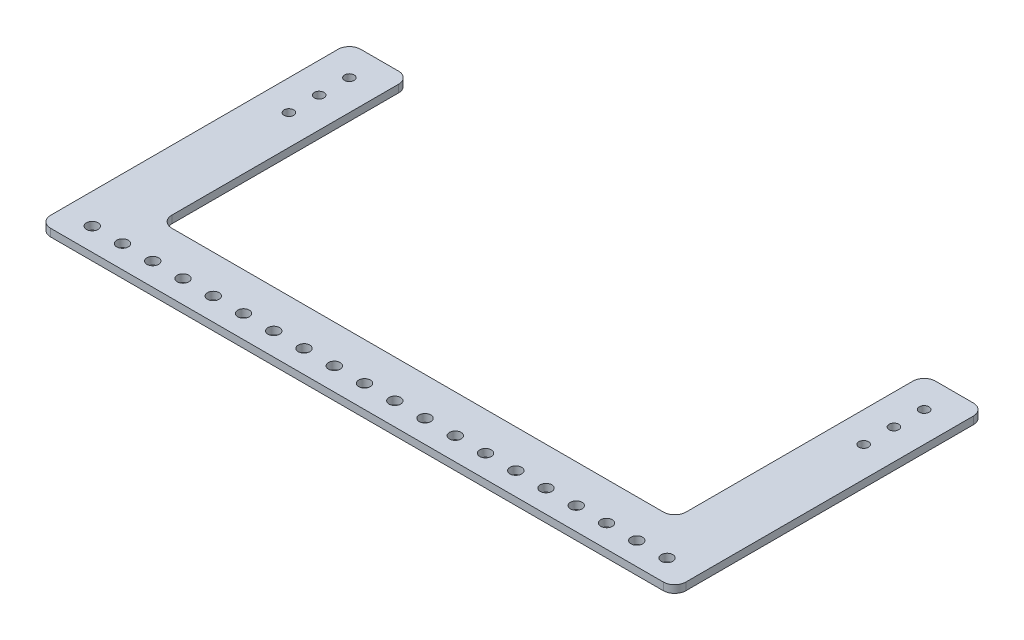
SolidWorks part; units mm, degrees
material "6061-T6 (SS)"
ref_plane "Front Plane" through (0, 0, 0) normal (0, 0, 1) x (1, 0, 0)
ref_plane "Top Plane" through (0, 0, 0) normal (0, 1, 0) x (1, 0, 0)
ref_plane "Right Plane" through (0, 0, 0) normal (1, 0, 0) x (0, 0, -1)
sketch "Sketch2" plane through (0, 0, 0) normal (0, 1, 0) x (1, 0, 0)
  line L0 (0, 65.0875) -> (0, -65.0875) construction
  line L1 (-133.35, -65.0875) -> (133.35, -65.0875)
  line L2 (-133.35, -65.0875) -> (-133.35, 65.0875)
  line L3 (-133.35, 65.0875) -> (133.35, 65.0875)
  line L4 (133.35, -65.0875) -> (133.35, 65.0875)
  line L5 (-133.35, -65.0875) -> (133.35, 65.0875) construction
  line L6 (-133.35, 65.0875) -> (133.35, -65.0875) construction
  line L7 (-107.95, 65.0875) -> (107.95, 65.0875)
  line L8 (-107.95, 65.0875) -> (-107.95, -39.624)
  line L9 (-107.95, -39.624) -> (107.95, -39.624)
  line L10 (107.95, 65.0875) -> (107.95, -39.624)
  line L11 (133.35, 65.0875) -> (107.95, 65.0875) construction
  line L12 (133.35, 65.0875) -> (133.35, -39.624) construction
  line L13 (133.35, -39.624) -> (107.95, -39.624) construction
  line L14 (107.95, 65.0875) -> (107.95, -39.624) construction
  circle A0 centre (-120.65, 52.3875) radius 2.0193
  circle A1 centre (-120.65, 39.6875) radius 2.0193
  circle A2 centre (-120.65, 26.9875) radius 2.0193
  circle A6 centre (120.65, 26.9875) radius 2.0193
  circle A7 centre (120.65, 39.6875) radius 2.0193
  circle A8 centre (120.65, 52.3875) radius 2.0193
  point P0 (0, 0)
  point P10 (0, -39.624)
  point P11 (0, -65.0875)
  dimension "D8" = 4.0386
  dimension "D1" = 266.7
  dimension "D2" = 130.175
  dimension "D3" = 215.9
  dimension "D4" = 25.4635
  dimension "D5" = 12.7
  dimension "D6" = 12.7
  dimension "D7" = 12.7
  dimension "D9" = 12.7
  dimension "D10" = 12.7
  dimension "D11" = 12.7
extrude "Boss-Extrude1" add sketch "Sketch2" along normal blind 3.175 contours L3 L10 L9 L8 L2 L1 L4 A7 A0 A1 A2 A6 A8 region at (-130.3823, 0, 0)
fillet "Fillet1" radius 4.7625 8 edges at (133.35, 1.5875, -65.0875) (-133.35, 1.5875, 65.0875) (-133.35, 1.5875, -65.0875) (-107.95, 1.5875, -65.0875) (-107.95, 1.5875, 39.624) (107.95, 1.5875, 39.624) (107.95, 1.5875, -65.0875) (133.35, 1.5875, 65.0875)
sketch "Sketch3" plane through (0, 3.175, 0) normal (0, 1, 0) x (1, 0, 0)
  line L0 (-133.35, -60.325) -> (-133.35, 60.325) construction
  line L1 (-128.5875, -65.0875) -> (128.5875, -65.0875) construction
  line L2 (0, -39.624) -> (0, -65.0875) construction
  line L3 (-103.1875, -39.624) -> (103.1875, -39.624) construction
  circle A0 centre (-120.65, -55.5625) radius 2.4384
  circle A19 centre (-107.95, -55.5625) radius 2.4384
  circle A20 centre (-95.25, -55.5625) radius 2.4384
  circle A21 centre (-82.55, -55.5625) radius 2.4384
  circle A22 centre (-69.85, -55.5625) radius 2.4384
  circle A23 centre (-57.15, -55.5625) radius 2.4384
  circle A24 centre (-44.45, -55.5625) radius 2.4384
  circle A25 centre (-31.75, -55.5625) radius 2.4384
  circle A26 centre (-19.05, -55.5625) radius 2.4384
  circle A27 centre (-6.35, -55.5625) radius 2.4384
  circle A28 centre (6.35, -55.5625) radius 2.4384
  circle A29 centre (19.05, -55.5625) radius 2.4384
  circle A30 centre (31.75, -55.5625) radius 2.4384
  circle A31 centre (44.45, -55.5625) radius 2.4384
  circle A32 centre (57.15, -55.5625) radius 2.4384
  circle A33 centre (69.85, -55.5625) radius 2.4384
  circle A34 centre (82.55, -55.5625) radius 2.4384
  circle A35 centre (95.25, -55.5625) radius 2.4384
  circle A36 centre (107.95, -55.5625) radius 2.4384
  circle A37 centre (120.65, -55.5625) radius 2.4384
  dimension "D1" = 4.8768
  dimension "D5" = 12.7
  dimension "D2" = 12.7
  dimension "D3" = 9.525
  dimension "D4" = 20
extrude "Cut-Extrude1" cut sketch "Sketch3" against normal through all
